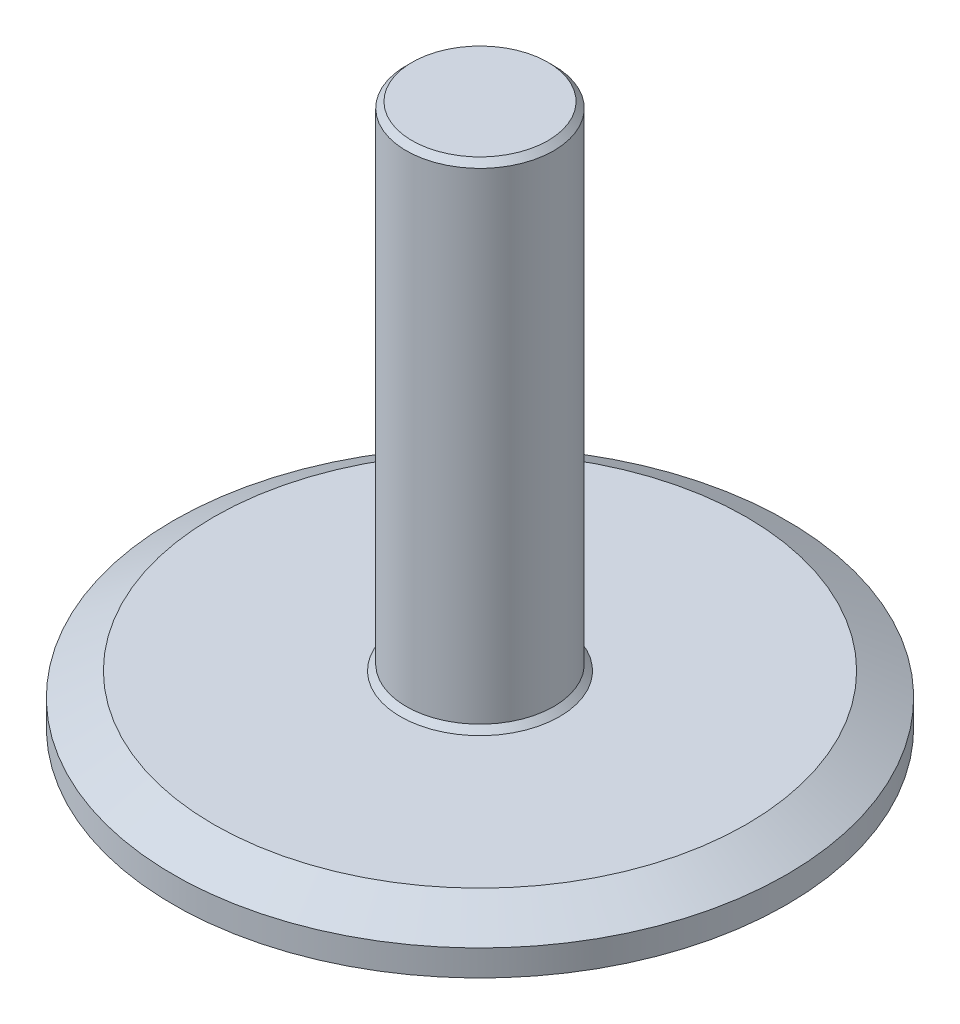
SolidWorks part; units mm, degrees
ref_plane "Front Plane" through (0, 0, 0) normal (0, 0, 1) x (1, 0, 0)
ref_plane "Top Plane" through (0, 0, 0) normal (0, 1, 0) x (1, 0, 0)
ref_plane "Right Plane" through (0, 0, 0) normal (1, 0, 0) x (0, 0, -1)
sketch "Sketch1" plane through (0, 0, 0) normal (0, 0, 1) x (1, 0, 0)
  line L0 (0, 0) -> (0, 70.85)
  line L1 (0, 70.85) -> (-9.5, 70.85)
  line L2 (-9.5, 70.85) -> (-9.5, 7.35)
  line L3 (-9.5, 7.35) -> (-39.5, 7.35)
  line L4 (-39.5, 7.35) -> (-39.5, 1)
  line L5 (-39.5, 1) -> (-32, 1)
  line L6 (-32, 1) -> (-32, 0)
  line L7 (-32, 0) -> (0, 0)
  dimension "D1" = 9.5
  dimension "D2" = 63.5
  dimension "D3" = 30
  dimension "D4" = 6.35
  dimension "D5" = 1
  dimension "D6" = 32
revolve "Revolve1" add sketch "Sketch1" angle 360 about L0
chamfer "Chamfer1" distance 0.75 angle 45 2 edges at (9.5, 7.35, 0) (9.5, 70.85, 0)
chamfer "Chamfer2" distance 3 angle 60 1 edges at (39.5, 7.35, 0) first distance on face at (39.5, 1, 0)
hole_wizard "1/4-28 Tapped Hole1" positions "Sketch2" profile "Sketch3" tap size "1/4-28" standard "ANSI Inch"
sketch "Sketch2" plane through (0, 0, 0) normal (0, -1, 0) x (-1, 0, 0)
  point P0 (0, 0)
sketch "Sketch3" plane through (0, 0, 0) normal (1, 0, 0) x (0, 0, -1)
  line L0 (0, 0) -> (0, 20.6254)
  line L1 (0, 20.6254) -> (2.7051, 19)
  line L2 (2.7051, 19) -> (2.7051, 0)
  line L5 (2.7051, 0) -> (0, 0)
  line L10 (0, 20.6254) -> (-2.7051, 19) construction
  line L11 (0, -6.35) -> (0, 107.95) construction
  dimension "Tap Drill Dia." = 5.4102
  dimension "Tap Drill Depth" = 19
  dimension "Drill Angle" = 118
cosmetic thread "Hole Thread1" parameters "D1"=12.7, "D2"=6.35
ref_axis "Axis1" through (0, 70.1, 0) along (0, -1, 0)
